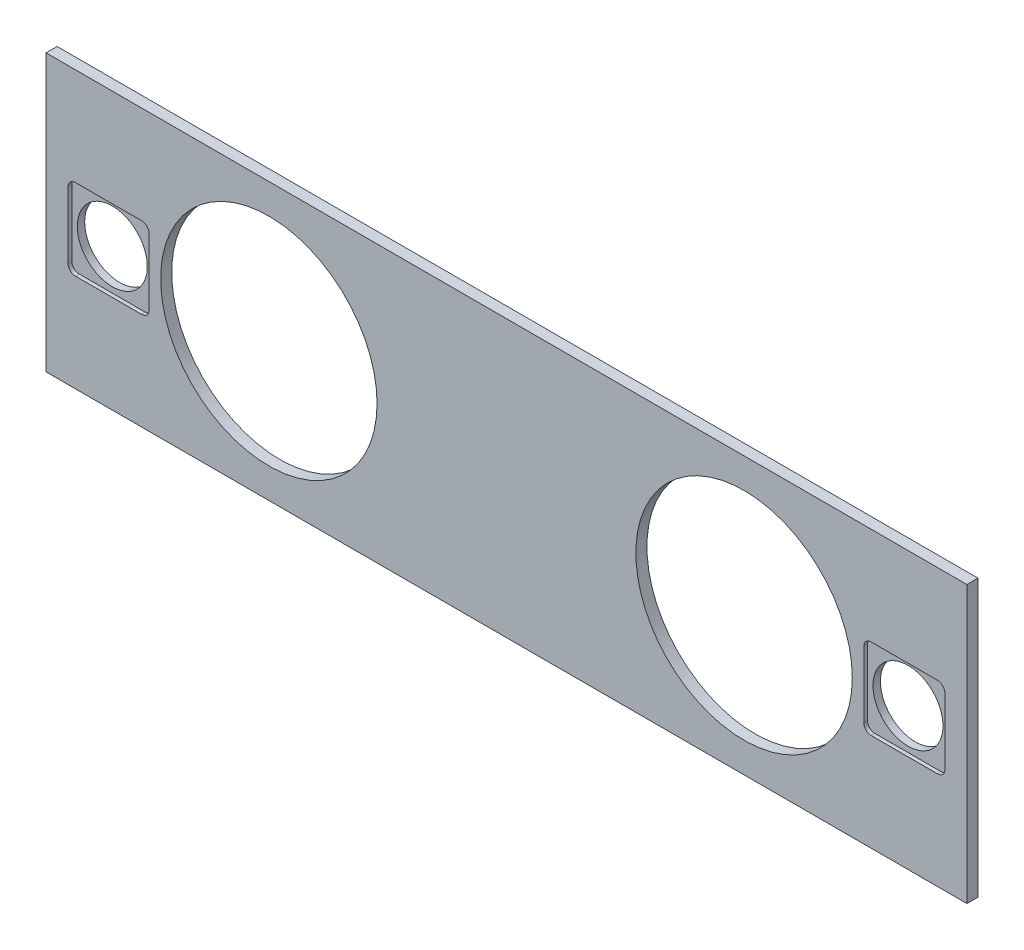
SolidWorks part; units mm, degrees
material "Pine"
ref_plane "Front Plane" through (0, 0, 0) normal (0, 0, 1) x (1, 0, 0)
ref_plane "Top Plane" through (0, 0, 0) normal (0, 1, 0) x (1, 0, 0)
ref_plane "Right Plane" through (0, 0, 0) normal (1, 0, 0) x (0, 0, -1)
sketch "Sketch1" plane through (0, 0, 0) normal (0, 0, 1) x (1, 0, 0)
  line L5 (500, 424.6951) -> (500, -112.2601) construction
  line L6 (0, 0) -> (1000, 0)
  line L10 (0, 0) -> (0, 300)
  line L11 (0, 300) -> (1000, 300)
  line L12 (1000, 0) -> (1000, 300)
  circle A0 centre (242, 150) radius 117.5
  circle A2 centre (758, 150) radius 117.5
  circle A3 centre (68, 150) radius 38
  circle A4 centre (932, 150) radius 38
  dimension "D1" = 235
  dimension "D8" = 76
  dimension "D2" = 1000
  dimension "D3" = 300
  dimension "D4" = 242
  dimension "D5" = 150
  dimension "D6" = 68
  dimension "D7" = 150
  dimension "D9" = 242
extrude "Boss-Extrude1" add sketch "Sketch1" along normal blind 12 contours A2 | A0 | L10 L11 L12 L6 | A3 | A4 region at (758, 150, 0)
sketch "Sketch4" plane through (0, 0, 12) normal (0, 0, 1) x (1, 0, 0)
  line L0 (0, 0) -> (0, 300) construction
  line L1 (32, 194) -> (104, 194)
  line L2 (24, 186) -> (24, 114)
  line L3 (32, 106) -> (104, 106)
  line L4 (112, 186) -> (112, 114)
  line L5 (0, 0) -> (0, 300) construction
  line L6 (0, 300) -> (1000, 300) construction
  line L7 (500, -84.0445) -> (500, 394.2312) construction
  line L8 (968, 106) -> (896, 106)
  line L9 (888, 186) -> (888, 114)
  line L10 (968, 194) -> (896, 194)
  line L11 (976, 186) -> (976, 114)
  arc A0 (104, 194) -> (112, 186) centre (104, 186) cw
  arc A1 (104, 106) -> (112, 114) centre (104, 114) ccw
  arc A2 (24, 114) -> (32, 106) centre (32, 114) ccw
  arc A3 (24, 186) -> (32, 194) centre (32, 186) cw
  arc A4 (896, 106) -> (888, 114) centre (896, 114) cw
  arc A5 (896, 194) -> (888, 186) centre (896, 186) ccw
  arc A6 (976, 114) -> (968, 106) centre (968, 114) cw
  arc A7 (976, 186) -> (968, 194) centre (968, 186) ccw
  point P16 (67.7235, 149.5451)
  dimension "D1" = 8
  dimension "D2" = 88
  dimension "D3" = 88
  dimension "D4" = 24
  dimension "D5" = 106
  dimension "D6" = 500
extrude "Cut-Extrude1" cut sketch "Sketch4" against normal blind 4 contours L2 A2 L3 A1 L4 A0 L1 A3 | L8 A4 L9 A5 L10 A7 L11 A6
equation "\"LENGTH\" = 1000mm"
equation "\"D2@Sketch1\"=\"LENGTH\""
equation "\"D6@Sketch4\"=\"LENGTH\"/2"
equation "\"PLY\"= 12mm"
equation "\"D1@Boss-Extrude1\"=\"PLY\""
